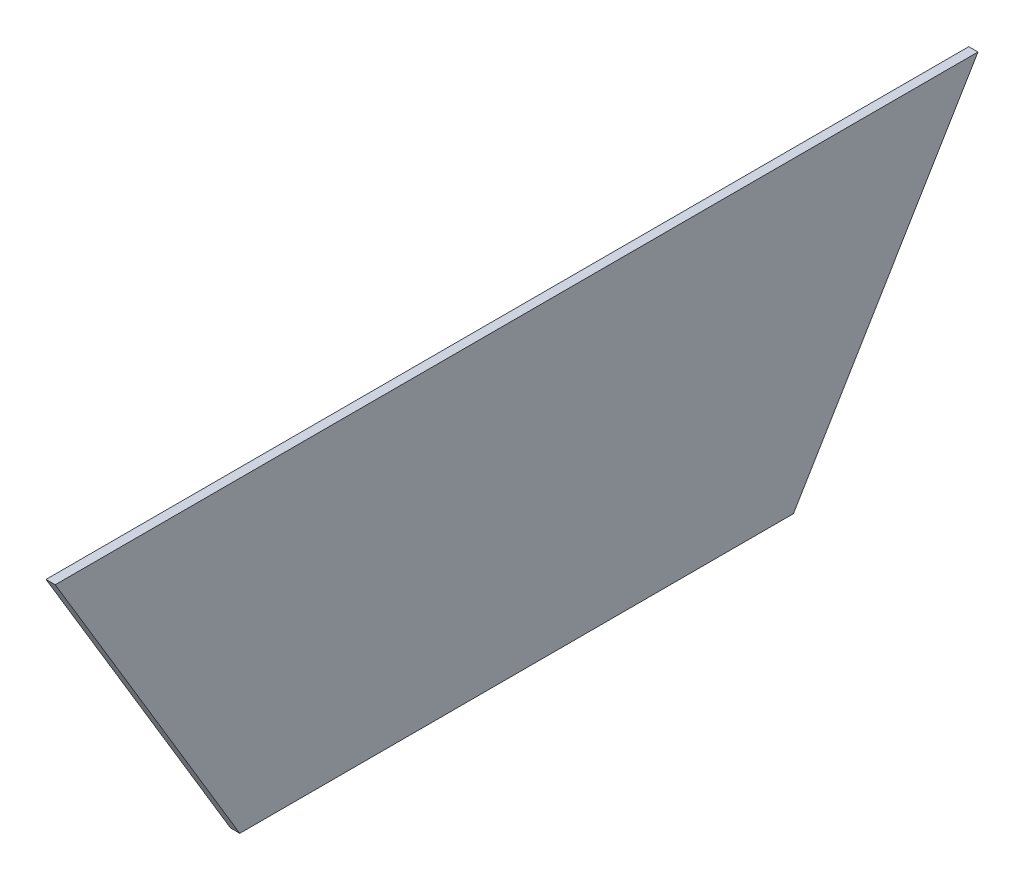
SolidWorks part; units mm, degrees
note: The reader was unsure of these and kept them because the rebuilt part matched: thickness of "Базовая кромка1", "Листовой металл3".
material "AISI 304"
ref_plane "Спереди" through (0, 0, 0) normal (0, 0, 1) x (1, 0, 0)
ref_plane "Сверху" through (0, 0, 0) normal (0, 1, 0) x (1, 0, 0)
ref_plane "Справа" through (0, 0, 0) normal (1, 0, 0) x (0, 0, -1)
sketch "Эскиз1" plane through (0, 0, 0) normal (1, 0, 0) x (0, 0, -1)
  line L0 (-90, 0) -> (90, 0)
  line L1 (90, 0) -> (150, 100)
  line L2 (150, 100) -> (-150, 100)
  line L3 (-150, 100) -> (-90, 0)
  line L4 (0, 100) -> (0, 0) construction
  dimension "D1" = 300
  dimension "D2" = 180
  dimension "D3" = 100
base flange "Базовая кромка1" sketch "Эскиз1" thickness 3 reverse thickness direction no parameters "D1"=4
sketch "Сгиб-Линии1" plane through (0, 0, 0) normal (0, 1, 0) x (1, 0, 0)
sketch "Граничная рамка1" plane through (0, 0, 0) normal (0, 1, 0) x (1, 0, 0)
sheet metal parameters "Листовой металл3" thickness 3 parameters "D1"=4
flat pattern "Развертка3" [suppressed]
sketch "Сгиб-Линии2" plane through (0, 0, 0) normal (0, 1, 0) x (1, 0, 0)
sketch "Граничная рамка2" [suppressed] plane through (0, 0, 0) normal (0, 1, 0) x (1, 0, 0)
